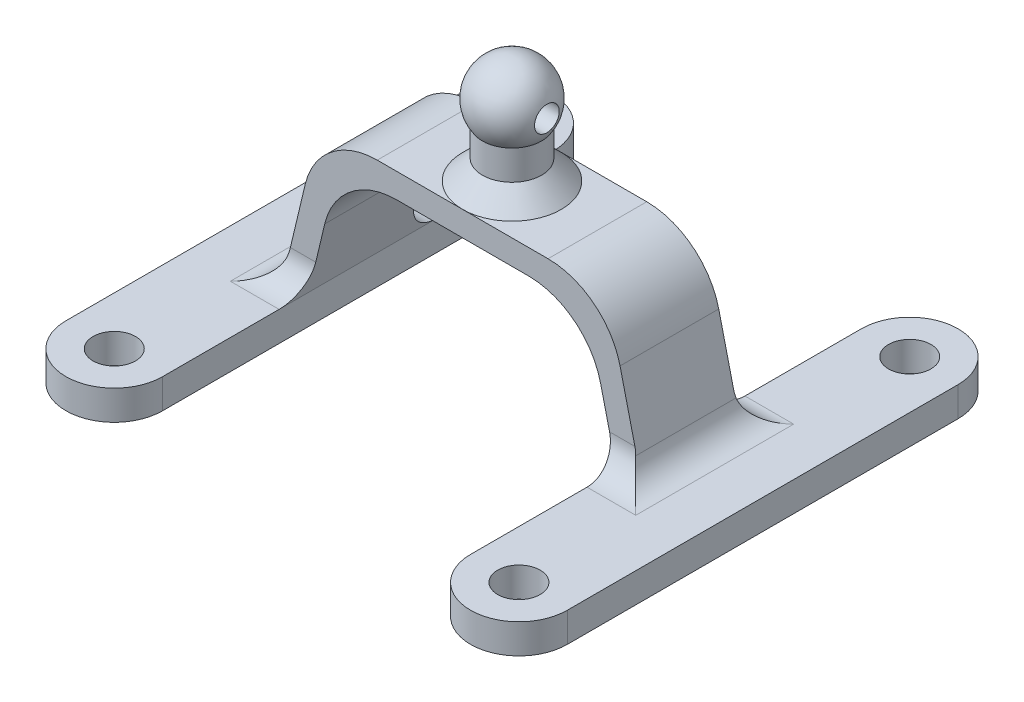
SolidWorks part; units mm, degrees
ref_plane "正面" through (0, 0, 0) normal (0, 0, 1) x (1, 0, 0)
ref_plane "平面" through (0, 0, 0) normal (0, 1, 0) x (1, 0, 0)
ref_plane "右側面" through (0, 0, 0) normal (1, 0, 0) x (0, 0, -1)
sketch "ｽｹｯﾁ1" plane through (0, 0, 0) normal (0, 0, 1) x (1, 0, 0)
  line L0 (-42.5, 17.9285) -> (-42.5, 20.9285) construction
  line L1 (-42.5, 20.9285) -> (42.5, 20.9285) construction
  line L2 (-42.5, 17.9285) -> (-42.5, 20.9285) construction
  line L3 (42.5, 17.9285) -> (-42.5, 17.9285) construction
  line L4 (42.5, 20.9285) -> (42.5, 17.9285) construction
  line L5 (42.5, 20.9285) -> (42.5, 17.9285) construction
  line L6 (9.5, -34) -> (0, -34) construction
  line L7 (0, -34) -> (-9.5, -34) construction
  line L8 (-9.5, -34) -> (-9.5, -32.085) construction
  line L9 (-9.5, -32.085) -> (-10, -32.085) construction
  line L10 (-12, -30.085) -> (-12, 30.085) construction
  line L11 (-10, 32.085) -> (-9.5, 32.085) construction
  line L12 (-9.5, 32.085) -> (-9.5, 34) construction
  line L13 (-9.5, 34) -> (0, 34) construction
  line L14 (0, 34) -> (9.5, 34) construction
  line L15 (9.5, 34) -> (9.5, 32.085) construction
  line L16 (9.5, 32.085) -> (10, 32.085) construction
  line L17 (12, 30.085) -> (12, -30.085) construction
  line L18 (10, -32.085) -> (9.5, -32.085) construction
  line L19 (9.5, -32.085) -> (9.5, -34) construction
  line L20 (-42.5, 17.9285) -> (-42.5, 20.9285)
  line L21 (-42.5, 20.9285) -> (42.5, 20.9285)
  line L22 (-42.5, 17.9285) -> (-42.5, 20.9285)
  line L23 (42.5, 17.9285) -> (-42.5, 17.9285)
  line L24 (42.5, 20.9285) -> (42.5, 17.9285)
  line L25 (42.5, 20.9285) -> (42.5, 17.9285)
  line L26 (9.5, -34) -> (0, -34)
  line L27 (0, -34) -> (-9.5, -34)
  line L28 (-9.5, -34) -> (-9.5, -32.085)
  line L29 (-9.5, -32.085) -> (-10, -32.085)
  line L30 (-12, -30.085) -> (-12, 30.085)
  line L31 (-10, 32.085) -> (-9.5, 32.085)
  line L32 (-9.5, 32.085) -> (-9.5, 34)
  line L33 (-9.5, 34) -> (0, 34)
  line L34 (0, 34) -> (9.5, 34)
  line L35 (9.5, 34) -> (9.5, 32.085)
  line L36 (9.5, 32.085) -> (10, 32.085)
  line L37 (12, 30.085) -> (12, -30.085)
  line L38 (10, -32.085) -> (9.5, -32.085)
  line L39 (9.5, -32.085) -> (9.5, -34)
  arc A0 (-12, -30.085) -> (-10, -32.085) centre (-10, -30.085) ccw construction
  arc A1 (-10, 32.085) -> (-12, 30.085) centre (-10, 30.085) ccw construction
  arc A2 (12, 30.085) -> (10, 32.085) centre (10, 30.085) ccw construction
  arc A3 (10, -32.085) -> (12, -30.085) centre (10, -30.085) ccw construction
  arc A4 (-12, -30.085) -> (-10, -32.085) centre (-10, -30.085) ccw
  arc A5 (-10, 32.085) -> (-12, 30.085) centre (-10, 30.085) ccw
  arc A6 (12, 30.085) -> (10, 32.085) centre (10, 30.085) ccw
  arc A7 (10, -32.085) -> (12, -30.085) centre (10, -30.085) ccw
sketch "ｽｹｯﾁ3" plane through (0, 0, 0) normal (0, 1, 0) x (1, 0, 0)
  circle A1 centre (20.5, 19.799) radius 2.15
  circle A2 centre (20.5, 19.799) radius 2.15
  circle A3 centre (-20.5, 19.799) radius 2.15
  circle A4 centre (-20.5, 19.799) radius 2.15
  circle A5 centre (20.5, -19.799) radius 2.15
  circle A6 centre (20.5, -19.799) radius 2.15
  circle A7 centre (-20.5, -19.799) radius 2.15
  circle A8 centre (-20.5, -19.799) radius 2.15
  arc A22 (-28.6236, -15.3929) -> (-23.9259, -16.1571) centre (-25.9814, -13.972) ccw
  arc A23 (-28.6236, 15.3929) -> (-28.6236, -15.3929) centre (0, 0) ccw
  arc A24 (-23.9259, 16.1571) -> (-28.6236, 15.3929) centre (-25.9814, 13.972) ccw
  arc A25 (-23.9259, 16.1571) -> (-16.9795, 23.3495) centre (-20.5, 19.799) ccw
  arc A26 (-16.3791, 28.0709) -> (-16.9795, 23.3495) centre (-14.8672, 25.4798) ccw
  arc A27 (16.3791, 28.0709) -> (-16.3791, 28.0709) centre (0, 0) ccw
  arc A28 (16.9795, 23.3495) -> (16.3791, 28.0709) centre (14.8672, 25.4798) ccw
  arc A29 (16.9795, 23.3495) -> (23.9259, 16.1571) centre (20.5, 19.799) ccw
  arc A30 (28.6236, 15.3929) -> (23.9259, 16.1571) centre (25.9814, 13.972) ccw
  arc A31 (28.6236, -15.3929) -> (28.6236, 15.3929) centre (0, 0) ccw
  arc A32 (23.9259, -16.1571) -> (28.6236, -15.3929) centre (25.9814, -13.972) ccw
  arc A33 (23.9259, -16.1571) -> (16.9795, -23.3495) centre (20.5, -19.799) ccw
  arc A34 (16.3791, -28.0709) -> (16.9795, -23.3495) centre (14.8672, -25.4798) ccw
  arc A35 (-16.3791, -28.0709) -> (16.3791, -28.0709) centre (0, 0) ccw
  arc A36 (-16.9795, -23.3495) -> (-16.3791, -28.0709) centre (-14.8672, -25.4798) ccw
  arc A37 (-16.9795, -23.3495) -> (-23.9259, -16.1571) centre (-20.5, -19.799) ccw
  arc A38 (-28.6236, -15.3929) -> (-23.9259, -16.1571) centre (-25.9814, -13.972) ccw
  arc A39 (-28.6236, 15.3929) -> (-28.6236, -15.3929) centre (0, 0) ccw
  arc A40 (-23.9259, 16.1571) -> (-28.6236, 15.3929) centre (-25.9814, 13.972) ccw
  arc A41 (-23.9259, 16.1571) -> (-16.9795, 23.3495) centre (-20.5, 19.799) ccw
  arc A42 (-16.3791, 28.0709) -> (-16.9795, 23.3495) centre (-14.8672, 25.4798) ccw
  arc A43 (16.3791, 28.0709) -> (-16.3791, 28.0709) centre (0, 0) ccw
  arc A44 (16.9795, 23.3495) -> (16.3791, 28.0709) centre (14.8672, 25.4798) ccw
  arc A45 (16.9795, 23.3495) -> (23.9259, 16.1571) centre (20.5, 19.799) ccw
  arc A46 (28.6236, 15.3929) -> (23.9259, 16.1571) centre (25.9814, 13.972) ccw
  arc A47 (28.6236, -15.3929) -> (28.6236, 15.3929) centre (0, 0) ccw
  arc A48 (23.9259, -16.1571) -> (28.6236, -15.3929) centre (25.9814, -13.972) ccw
  arc A49 (23.9259, -16.1571) -> (16.9795, -23.3495) centre (20.5, -19.799) ccw
  arc A50 (16.3791, -28.0709) -> (16.9795, -23.3495) centre (14.8672, -25.4798) ccw
  arc A51 (-16.3791, -28.0709) -> (16.3791, -28.0709) centre (0, 0) ccw
  arc A52 (-16.9795, -23.3495) -> (-16.3791, -28.0709) centre (-14.8672, -25.4798) ccw
  arc A53 (-16.9795, -23.3495) -> (-23.9259, -16.1571) centre (-20.5, -19.799) ccw
  dimension "D1" = 0
  dimension "D2" = 0
  dimension "D3" = 0
  dimension "D4" = 0
  dimension "D5" = 0
ref_plane "平面1" through (0, 20.9285, 0) normal (0, 1, 0) x (1, 0, 0)
sketch "ｽｹｯﾁ4" plane through (0, 20.9285, 0) normal (0, 1, 0) x (1, 0, 0)
  line L0 (-20.5, 19.799) -> (-20.5, -19.799) construction
  line L1 (-15.6, 19.799) -> (-15.6, -19.799)
  line L2 (-25.4, 19.799) -> (-25.4, -19.799)
  line L3 (20.5, 19.799) -> (20.5, -19.799) construction
  line L4 (25.4, 19.799) -> (25.4, -19.799)
  line L5 (15.6, 19.799) -> (15.6, -19.799)
  circle A0 centre (20.5, 19.799) radius 2.15 construction
  circle A1 centre (20.5, -19.799) radius 2.15 construction
  circle A2 centre (-20.5, -19.799) radius 2.15 construction
  circle A3 centre (-20.5, 19.799) radius 2.15 construction
  circle A4 centre (20.5, 19.799) radius 2.15
  circle A5 centre (20.5, -19.799) radius 2.15
  circle A6 centre (-20.5, -19.799) radius 2.15
  circle A7 centre (-20.5, 19.799) radius 2.15
  circle A8 centre (-20.5, 19.799) radius 4.9
  circle A9 centre (20.5, 19.799) radius 4.9
  circle A10 centre (20.5, -19.799) radius 4.9
  circle A11 centre (-20.5, -19.799) radius 4.9
  arc A12 (-15.6, 19.799) -> (-25.4, 19.799) centre (-20.5, 19.799) ccw
  arc A13 (-25.4, -19.799) -> (-15.6, -19.799) centre (-20.5, -19.799) ccw
  arc A14 (25.4, 19.799) -> (15.6, 19.799) centre (20.5, 19.799) ccw
  arc A15 (15.6, -19.799) -> (25.4, -19.799) centre (20.5, -19.799) ccw
  point P20 (-20.5, 0)
  point P25 (20.5, 0)
  dimension "D1" = 2.75
extrude "ﾎﾞｽ - 押し出し1" add sketch "ｽｹｯﾁ4" along normal blind 3 contours A8 A7 | A11 L1 A8 L2 | A11 A6 | A10 L4 A9 L5 | A9 A4 | A10 A5 region at (-20.5, 20.9285, -15.0376) region at (-20.5, 20.9285, 0) region at (-20.5, 20.9285, 24.5604) region at (20.5, 20.9285, -15.0376) region at (20.5, 20.9285, 0) region at (20.5, 20.9285, 24.5604)
sketch "ｽｹｯﾁ5" plane through (0, 0, 0) normal (1, 0, 0) x (0, 0, -1)
  circle A0 centre (0, 0) radius 34
  circle A1 centre (0, 0) radius 34
sketch "ｽｹｯﾁ7" plane through (0, 0, 0) normal (0, 0, 1) x (1, 0, 0)
  line L0 (12, 30.085) -> (12, -30.085) construction
  line L1 (9.5, 32.085) -> (10, 32.085) construction
  line L2 (9.5, 34) -> (9.5, 32.085) construction
  line L3 (0, 34) -> (9.5, 34) construction
  line L4 (-9.5, 34) -> (0, 34) construction
  line L5 (-9.5, 32.085) -> (-9.5, 34) construction
  line L6 (-10, 32.085) -> (-9.5, 32.085) construction
  line L7 (-12, -30.085) -> (-12, 30.085) construction
  line L8 (12, 30.085) -> (12, -30.085) construction
  line L9 (9.5, 32.085) -> (10, 32.085) construction
  line L10 (9.5, 34) -> (9.5, 32.085) construction
  line L11 (0, 34) -> (9.5, 34) construction
  line L12 (-9.5, 34) -> (0, 34) construction
  line L13 (-9.5, 32.085) -> (-9.5, 34) construction
  line L14 (-10, 32.085) -> (-9.5, 32.085) construction
  line L15 (-12, -30.085) -> (-12, 30.085) construction
  line L16 (-15.6, 20.9285) -> (-25.4, 20.9285)
  line L17 (-15.6, 20.9285) -> (-25.4, 20.9285)
  line L18 (-25.4, 20.9285) -> (-25.4, 23.9285)
  line L19 (-25.4, 20.9285) -> (-25.4, 23.9285)
  line L20 (-25.4, 23.9285) -> (-15.6, 23.9285)
  line L21 (-25.4, 23.9285) -> (-15.6, 23.9285)
  line L22 (-15.6, 23.9285) -> (-15.6, 20.9285)
  line L23 (-15.6, 23.9285) -> (-15.6, 20.9285)
  line L24 (25.4, 20.9285) -> (15.6, 20.9285)
  line L25 (25.4, 20.9285) -> (15.6, 20.9285)
  line L26 (15.6, 20.9285) -> (15.6, 23.9285)
  line L27 (15.6, 20.9285) -> (15.6, 23.9285)
  line L28 (15.6, 23.9285) -> (25.4, 23.9285)
  line L29 (15.6, 23.9285) -> (25.4, 23.9285)
  line L30 (25.4, 23.9285) -> (25.4, 20.9285)
  line L31 (25.4, 23.9285) -> (25.4, 20.9285)
  line L32 (-12.6, 36.5) -> (-15.6, 23.9285)
  line L33 (12.6, 36.5) -> (-12.6, 36.5)
  line L34 (0, 36.5) -> (0, 0) construction
  line L35 (0, 36.5) -> (0, 39)
  line L36 (-14.5736, 39) -> (14.5736, 39)
  line L37 (-14.5736, 39) -> (-18.1702, 23.9285)
  line L38 (12.6, 36.5) -> (15.6, 23.9285)
  line L39 (14.5736, 39) -> (18.1702, 23.9285)
  arc A0 (12, 30.085) -> (10, 32.085) centre (10, 30.085) ccw construction
  arc A1 (-10, 32.085) -> (-12, 30.085) centre (-10, 30.085) ccw construction
  arc A2 (12, 30.085) -> (10, 32.085) centre (10, 30.085) ccw construction
  arc A3 (-10, 32.085) -> (-12, 30.085) centre (-10, 30.085) ccw construction
  dimension "D1" = 2.5
  dimension "D2" = 2.5
  dimension "D3" = 2.5
  dimension "D4" = 3
extrude "ﾎﾞｽ - 押し出し2" add sketch "ｽｹｯﾁ7" along normal mid plane 10 contours L36 L21 L33 L35 | L36 L35 L33 L29 region at (-16.8851, 24.1646, 0) region at (0.2361, 37.75, 0)
fillet "ﾌｨﾚｯﾄ1" radius 7.5 4 edges at (14.5736, 39, 0) (12.6, 36.5, 0) (-12.6, 36.5, 0) (-14.5736, 39, 0)
fillet "ﾌｨﾚｯﾄ2" radius 3 6 edges at (16.8851, 23.9285, -5) (-16.8851, 23.9285, 5) (16.8851, 23.9285, 5) (-16.8851, 23.9285, -5) (18.1702, 23.9285, 0) (-18.1702, 23.9285, 0)
sketch "ｽｹｯﾁ8" plane through (0, 39, 0) normal (0, 1, 0) x (1, 0, 0)
  line L4 (-8.6528, -5) -> (8.6528, -5)
  line L5 (8.6528, -5) -> (8.6528, 5)
  line L6 (8.6528, 5) -> (-8.6528, 5)
  line L7 (8.6528, -5) -> (8.6528, 5)
  line L8 (-8.6528, -5) -> (8.6528, -5) construction
  line L10 (8.6528, 5) -> (-8.6528, 5) construction
  line L12 (-8.6528, 5) -> (-8.6528, -5)
  line L13 (-8.6528, 5) -> (-8.6528, -5)
  circle A0 centre (0, 0) radius 3
  dimension "D2" = 6
  dimension "D1" = 0
extrude "ﾎﾞｽ - 押し出し3" add sketch "ｽｹｯﾁ8" along normal blind 5 contours A0 region at (0, 39, 0)
sketch "ｽｹｯﾁ9" plane through (0, 0, 0) normal (0, 0, 1) x (1, 0, 0)
  line L0 (-3, 39) -> (-3, 44)
  line L1 (3, 44) -> (3, 39)
  line L2 (3, 44) -> (3, 39)
  line L3 (-3, 39) -> (-3, 44)
  line L6 (0, 50) -> (0, 46.25) construction
  line L7 (0, 42.5) -> (0, 50)
  circle A0 centre (0, 46.25) radius 3.75
  point P10 (0, 51.091)
  point P11 (0, 46.6259)
  dimension "D1" = 7.5
revolve "回転1" add sketch "ｽｹｯﾁ9" angle 360 about L6 region at (1.5915, 46.25, 0)
sketch "ｽｹｯﾁ10" plane through (0, 0, 0) normal (1, 0, 0) x (0, 0, -1)
  arc A0 (3, 44) -> (-3, 44) centre (0, 46.25) ccw
  arc A1 (3, 44) -> (-3, 44) centre (0, 46.25) ccw
  circle A2 centre (0, 46.25) radius 1.25
  dimension "D1" = 2.5
extrude "ｶｯﾄ - 押し出し1" cut sketch "ｽｹｯﾁ10" against normal mid plane 10 contours A2 region at (0, 46.25, 0)
chamfer "面取り1" distance 2 angle 45 1 edges at (0, 39, 3)
